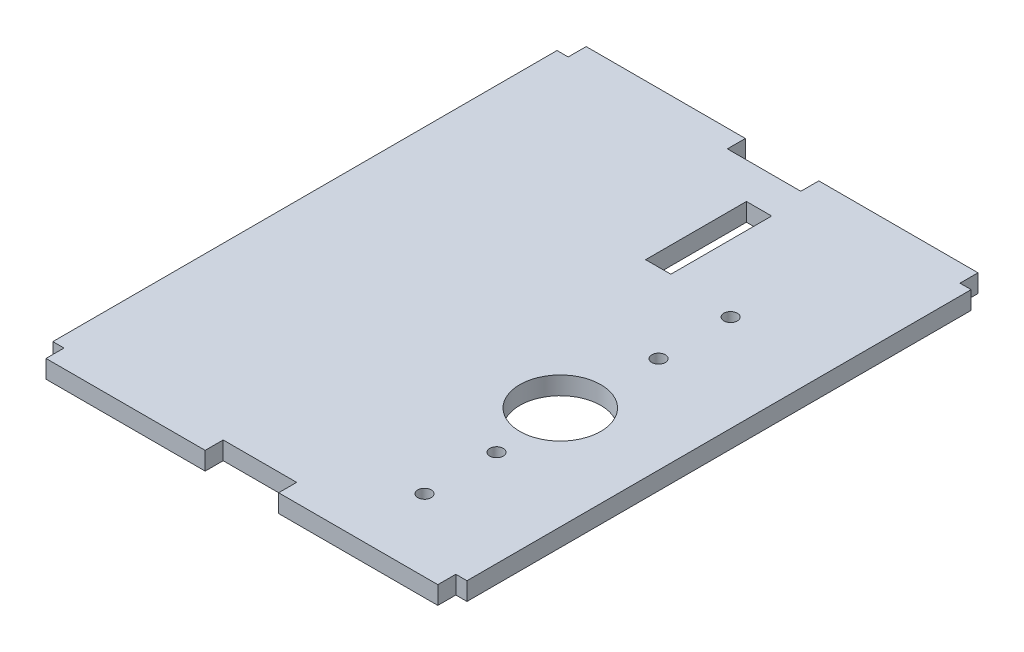
SolidWorks part; units mm, degrees
ref_plane "Front Plane" through (0, 0, 0) normal (0, 0, 1) x (1, 0, 0)
ref_plane "Top Plane" through (0, 0, 0) normal (0, 1, 0) x (1, 0, 0)
ref_plane "Right Plane" through (0, 0, 0) normal (1, 0, 0) x (0, 0, -1)
sketch "Sketch1" plane through (0, 0, 0) normal (0, 1, 0) x (1, 0, 0)
  line L1 (0, 0) -> (292.1, 0)
  line L2 (0, 0) -> (0, 355.6)
  line L3 (0, 355.6) -> (292.1, 355.6)
  line L4 (292.1, 0) -> (292.1, 355.6)
  ellipse E1 centre (219.5122, 138.3861) end of major axis (248.0872, 138.3861) minor radius 28.574
  dimension "D1" = 355.6
  dimension "D2" = 292.1
extrude "Boss-Extrude1" add sketch "Sketch1" along normal blind 12.7
sketch "Sketch2" plane through (0, 0, 0) normal (0, -1, 0) x (1, 0, 0)
  line L0 (0, 0) -> (292.1, 0) construction
  line L1 (0, -355.6) -> (0, 0) construction
  circle A0 centre (224.028, -38.1) radius 4.7625
  circle A1 centre (224.028, -88.9) radius 4.7625
  circle A2 centre (224.028, -203.2) radius 4.7625
  circle A3 centre (224.028, -254) radius 4.7625
  dimension "D3" = 88.9
  dimension "D6" = 9.525
  dimension "D1" = 38.1
  dimension "D2" = 224.028
  dimension "D4" = 203.2
  dimension "D5" = 254
  dimension "D7" = 224.028
  dimension "D8" = 224.028
  dimension "D9" = 224.028
extrude "Cut-Extrude1" cut sketch "Sketch2" against normal blind 12.7
sketch "Sketch3" plane through (0, 12.7, 0) normal (0, 1, 0) x (1, 0, 0)
  line L0 (146.05, 355.6) -> (146.05, 250.206) construction
  line L1 (0, 177.8) -> (22.2548, 177.8) construction
  line L2 (7.874, 355.6) -> (120.142, 355.6)
  line L3 (7.874, 355.6) -> (7.874, 368.3)
  line L4 (0, 355.6) -> (0, 0)
  line L5 (0, 0) -> (292.1, 0)
  line L6 (292.1, 0) -> (292.1, 355.6)
  line L7 (292.1, 355.6) -> (0, 355.6)
  line L8 (0, 355.6) -> (0, 0) construction
  line L9 (0, 0) -> (292.1, 0) construction
  line L10 (292.1, 0) -> (292.1, 355.6) construction
  line L11 (292.1, 355.6) -> (0, 355.6) construction
  line L12 (7.874, 368.3) -> (120.142, 368.3)
  line L13 (120.142, 355.6) -> (120.142, 368.3)
  line L14 (284.226, 368.3) -> (171.958, 368.3)
  line L15 (171.958, 355.6) -> (171.958, 368.3)
  line L16 (284.226, 355.6) -> (171.958, 355.6)
  line L17 (284.226, 355.6) -> (284.226, 368.3)
  line L18 (284.226, 0) -> (284.226, -12.7)
  line L19 (284.226, 0) -> (171.958, 0)
  line L20 (171.958, 0) -> (171.958, -12.7)
  line L21 (284.226, -12.7) -> (171.958, -12.7)
  line L22 (7.874, -12.7) -> (120.142, -12.7)
  line L23 (120.142, 0) -> (120.142, -12.7)
  line L24 (7.874, 0) -> (120.142, 0)
  line L25 (7.874, 0) -> (7.874, -12.7)
  dimension "D2" = 25.908
  dimension "D3" = 112.268
  dimension "D4" = 12.7
  dimension "D1" = 0
extrude "Boss-Extrude2" add sketch "Sketch3" against normal blind 12.7
sketch "Sketch4" plane through (0, 0, 0) normal (0, -1, 0) x (1, 0, 0)
  line L20 (0, 0) -> (0, -355.6)
  line L21 (0, -355.6) -> (7.874, -355.6)
  line L22 (7.874, -355.6) -> (7.874, -368.3)
  line L23 (7.874, -368.3) -> (120.142, -368.3)
  line L24 (120.142, -368.3) -> (120.142, -355.6)
  line L25 (120.142, -355.6) -> (171.958, -355.6)
  line L26 (171.958, -355.6) -> (171.958, -368.3)
  line L27 (171.958, -368.3) -> (284.226, -368.3)
  line L28 (284.226, -368.3) -> (284.226, -355.6)
  line L29 (284.226, -355.6) -> (292.1, -355.6)
  line L30 (292.1, -355.6) -> (292.1, 0)
  line L31 (292.1, 0) -> (284.226, 0)
  line L32 (284.226, 0) -> (284.226, 12.7)
  line L33 (284.226, 12.7) -> (171.958, 12.7)
  line L34 (171.958, 12.7) -> (171.958, 0)
  line L35 (171.958, 0) -> (120.142, 0)
  line L36 (120.142, 0) -> (120.142, 12.7)
  line L37 (120.142, 12.7) -> (7.874, 12.7)
  line L38 (7.874, 12.7) -> (7.874, 0)
  line L39 (7.874, 0) -> (0, 0)
  line L40 (0, 0) -> (0, -355.6)
  line L41 (0, -355.6) -> (7.874, -355.6)
  line L42 (7.874, -355.6) -> (7.874, -368.3)
  line L43 (7.874, -368.3) -> (120.142, -368.3)
  line L44 (120.142, -368.3) -> (120.142, -355.6)
  line L45 (120.142, -355.6) -> (171.958, -355.6)
  line L46 (171.958, -355.6) -> (171.958, -368.3)
  line L47 (171.958, -368.3) -> (284.226, -368.3)
  line L48 (284.226, -368.3) -> (284.226, -355.6)
  line L49 (284.226, -355.6) -> (292.1, -355.6)
  line L50 (292.1, -355.6) -> (292.1, 0)
  line L51 (292.1, 0) -> (284.226, 0)
  line L52 (284.226, 0) -> (284.226, 12.7)
  line L53 (284.226, 12.7) -> (171.958, 12.7)
  line L54 (171.958, 12.7) -> (171.958, 0)
  line L55 (171.958, 0) -> (120.142, 0)
  line L56 (120.142, 0) -> (120.142, 12.7)
  line L57 (120.142, 12.7) -> (7.874, 12.7)
  line L58 (7.874, 12.7) -> (7.874, 0)
  line L59 (7.874, 0) -> (0, 0)
  circle A5 centre (224.028, -203.2) radius 4.7625 construction
  circle A6 centre (224.028, -88.9) radius 4.7625 construction
  dimension "D3" = 109.5375
  dimension "D1" = 0
sketch "Sketch5" plane through (0, 12.7, 0) normal (0, 1, 0) x (1, 0, 0)
  line L0 (171.958, 368.3) -> (284.226, 368.3) construction
  line L2 (292.1, 355.6) -> (292.1, 0) construction
  line L4 (120.142, 355.6) -> (171.958, 355.6) construction
  line L5 (176.784, 330.2) -> (159.004, 330.2)
  line L6 (176.784, 330.2) -> (176.784, 259.08)
  line L7 (176.784, 259.08) -> (159.004, 259.08)
  line L8 (159.004, 330.2) -> (159.004, 259.08)
  point P10 (176.784, 330.2)
  dimension "D1" = 38.1
  dimension "D2" = 115.316
  dimension "D3" = 17.78
  dimension "D4" = 71.12
extrude "Cut-Extrude2" cut sketch "Sketch5" against normal through all
